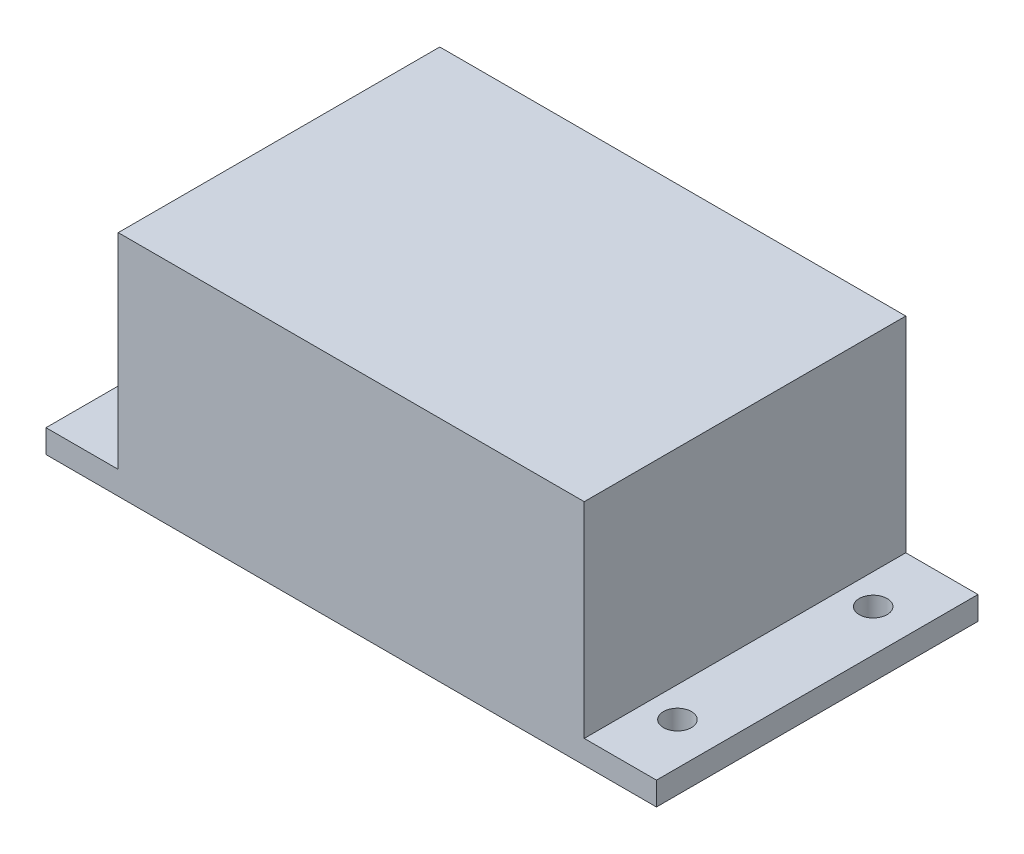
SolidWorks part; units mm, degrees
material "ABS"
ref_plane "前视基准面" through (0, 0, 0) normal (0, 0, 1) x (1, 0, 0)
ref_plane "上视基准面" through (0, 0, 0) normal (0, 1, 0) x (1, 0, 0)
ref_plane "右视基准面" through (0, 0, 0) normal (1, 0, 0) x (0, 0, -1)
sketch "草图1" plane through (0, 0, 0) normal (0, 1, 0) x (1, 0, 0)
  line L0 (-56.5, -21) -> (56.5, -21) construction
  line L1 (-65.5, -34.5) -> (65.5, -34.5)
  line L2 (-65.5, -34.5) -> (-65.5, 34.5)
  line L3 (-65.5, 34.5) -> (65.5, 34.5)
  line L4 (65.5, -34.5) -> (65.5, 34.5)
  line L5 (-65.5, -34.5) -> (65.5, 34.5) construction
  line L6 (-65.5, 34.5) -> (65.5, -34.5) construction
  line L7 (56.5, -21) -> (56.5, 21) construction
  line L8 (56.5, 21) -> (-56.5, 21) construction
  line L9 (-56.5, 21) -> (-56.5, -21) construction
  line L10 (-50, 34.5) -> (-50, -34.5)
  line L11 (50, 34.5) -> (50, -34.5)
  line L12 (-50, 0) -> (50, 0) construction
  circle A0 centre (56.5, 21) radius 3
  circle A1 centre (56.5, -21) radius 3
  circle A2 centre (-56.5, -21) radius 3
  circle A3 centre (-56.5, 21) radius 3
  point P0 (0, 0)
  point P14 (56.5, 24)
  point P15 (56.5, -24)
  point P16 (56.5, 18)
  point P17 (56.5, -18)
  point P18 (56.5, 0)
  point P19 (0, 21)
  point P20 (-53.5, 21)
  point P21 (-59.5, 21)
  point P22 (53.5, 21)
  point P23 (59.5, 21)
  point P30 (0, 0)
  dimension "D1" = 48
  dimension "D2" = 36
  dimension "D3" = 107
  dimension "D4" = 131
  dimension "D5" = 69
  dimension "D6" = 100
extrude "凸台-拉伸1" add sketch "草图1" along normal blind 5 contours L10 L3 L2 L1 A3 A2 | L3 L11 L1 L4 A1 A0 region at (-57.8198, 0, 0) region at (57.8198, 0, 0)
extrude "凸台-拉伸2" add sketch "草图1<3>" along normal blind 49 contours L11 L3 L10 L1 region at (0, 0, 0)
sketch "草图1<3>" plane through (0, 0, 0) normal (0, 1, 0) x (1, 0, 0) same geometry as "草图1"
